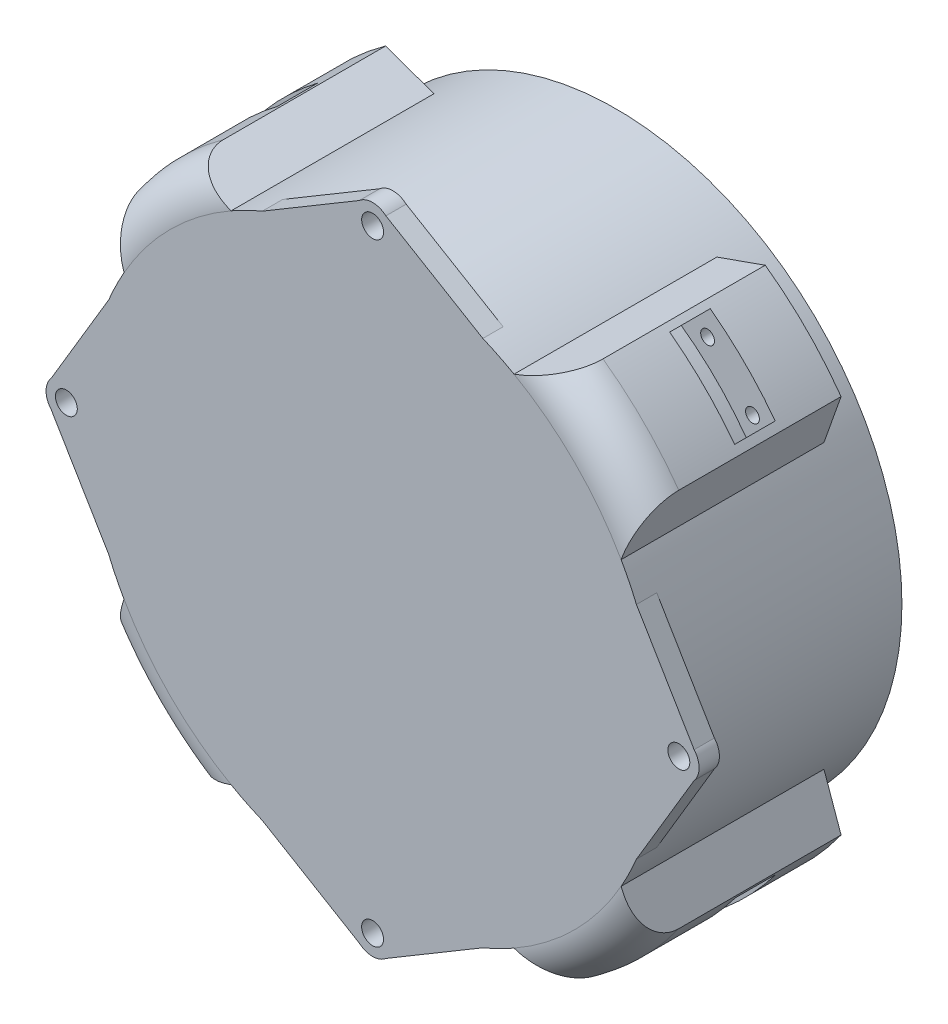
SolidWorks part; units mm, degrees
ref_plane "Front Plane" through (0, 0, 0) normal (0, 0, 1) x (1, 0, 0)
ref_plane "Top Plane" through (0, 0, 0) normal (0, 1, 0) x (1, 0, 0)
ref_plane "Right Plane" through (0, 0, 0) normal (1, 0, 0) x (0, 0, -1)
sketch "Sketch2" plane through (0, 0, 0) normal (0, 0, 1) x (1, 0, 0)
  line L1 (-38.5, -15.5) -> (-38.5, 15.5)
  line L2 (-33.5, 15.5) -> (33.5, 15.5)
  line L3 (-33.5, 15.5) -> (-33.5, -15.5)
  line L4 (-33.5, -15.5) -> (33.5, -15.5)
  line L5 (33.5, 15.5) -> (33.5, -15.5)
  line L6 (-33.5, 15.5) -> (33.5, -15.5) construction
  line L7 (-33.5, -15.5) -> (33.5, 15.5) construction
  line L8 (-38.5, 15.5) -> (-38.5, 20.5)
  line L9 (-38.5, 20.5) -> (33.5, 20.5)
  line L10 (0, -15.5) -> (0, -9.7241)
  line L11 (38.5, 20.5) -> (-33.5, 20.5)
  line L12 (38.5, 15.5) -> (38.5, 20.5)
  line L13 (38.5, -15.5) -> (38.5, 15.5)
  line L14 (38.5, -15.5) -> (38.5, -20.5)
  line L15 (38.5, -20.5) -> (-38.5, -20.5)
  line L16 (-38.5, -20.5) -> (-38.5, -15.5)
  line L17 (38.5, -20.5) -> (-38.5, -20.5)
  line L18 (38.5, -20.5) -> (38.5, 20.5)
  line L19 (38.5, 20.5) -> (-38.5, 20.5)
  line L20 (-38.5, -20.5) -> (-38.5, 20.5)
  point P2 (0, 0)
extrude "Boss-Extrude1" add sketch "Sketch2" against normal blind 30.4 contours L16 L15 L14 L13 L12 L11 L9 L8 L1 L2 L5 L4 L3 region at (-37.6276, 0, 0)
sketch "Sketch3" plane through (0, 0, 0) normal (0, 0, 1) x (1, 0, 0)
  line L1 (38.5, -20.5) -> (-38.5, -20.5)
  line L2 (38.5, -20.5) -> (38.5, 20.5)
  line L3 (38.5, 20.5) -> (-38.5, 20.5)
  line L4 (-38.5, -20.5) -> (-38.5, 20.5)
extrude "Boss-Extrude2" add sketch "Sketch3" along normal blind 5
sketch "Sketch4" plane through (-38.5, 0, 0) normal (-1, 0, 0) x (0, 0, 1)
  line L0 (5, 0) -> (0, 0)
  line L1 (5, 20.5) -> (5, -20.5) construction
  line L2 (0, 0) -> (-7, 0)
  line L4 (-10, -8) -> (-4, -8)
  line L5 (-10, -8) -> (-10, 8)
  line L6 (-10, 8) -> (-4, 8)
  line L7 (-4, -8) -> (-4, 8)
  line L8 (-10, -8) -> (-4, 8) construction
  line L9 (-10, 8) -> (-4, -8) construction
extrude "Cut-Extrude1" cut sketch "Sketch4" against normal blind 24 contours L4 L7 L6 L5 region at (-38.5, 0, -9.8291)
sketch "Sketch6" plane through (0, 0, 5) normal (0, 0, 1) x (1, 0, 0)
  circle A0 centre (-19.5, 0) radius 65.5
extrude "Boss-Extrude3" add sketch "Sketch6" against normal blind 5
sketch "Sketch7" plane through (0, 0, 5) normal (0, 0, 1) x (1, 0, 0)
  line L0 (-85, 0) -> (-90, 0)
  circle A1 centre (-19.5, 0) radius 65.5 construction
  circle A2 centre (-19.5, 0) radius 70.5
  circle A3 centre (-19.5, 0) radius 65.5
  circle M3 centre (-19.5, 0) radius 65.5
extrude "Boss-Extrude4" add sketch "Sketch7" against normal blind 60 contours A2 M3 region at (-19.5, 68.506, 5)
sketch "Sketch8" plane through (0, 0, 0) normal (0, 0, -1) x (-1, 0, 0)
  line L1 (19.5, -45.5) -> (29.5, -45.5)
  line L2 (29.5, -45.5) -> (29.5, -35.5)
  line L3 (29.5, -35.5) -> (9.5, -35.5)
  line L4 (9.5, -35.5) -> (9.5, -45.5)
  line L5 (9.5, -45.5) -> (19.9696, -45.5)
extrude "Boss-Extrude5" add sketch "Sketch8" along normal blind 56 contours L4 L5 L1 L2 L3 region at (-19.5, -40.5, 0)
ref_plane "Plane1" through (0, 0, 0) normal (0, -1, 0) x (-1, 0, 0)
sketch "Sketch17" plane through (-38.5, 0, 0) normal (-1, 0, 0) x (0, 0, 1)
  line L1 (-10, -8) -> (-4, -8)
  line L2 (-10, -8) -> (-10, 8)
  line L3 (-10, 8) -> (-4, 8)
  line L4 (-4, -8) -> (-4, 8)
extrude "Cut-Extrude7" cut sketch "Sketch17" along normal blind 64
sketch "Sketch19" plane through (0, -45.5, 0) normal (0, -1, 0) x (-1, 0, 0)
  line L0 (19.5, 56.8) -> (19.5, 52.8)
  line L1 (-51, 56.8) -> (90, 56.8) construction
  line L2 (9.5, 56) -> (17.1, 56)
  line L3 (9.5, 56) -> (29.5, 56) construction
  line L4 (21.9, 56) -> (29.5, 56)
  line L5 (13.3, 56) -> (9.5, 0)
  line L6 (25.7, 56) -> (29.5, 0)
  line L7 (29.5, 0) -> (29.5, 54.5391)
  line L8 (29.5, 56) -> (29.5, 0) construction
  line L9 (9.5, 0) -> (9.5, 55.2956)
  line L10 (9.5, 56) -> (9.5, 0) construction
  circle A0 centre (19.5, 52.8) radius 1.7
  circle A1 centre (19.5, 52.8) radius 4
  line M5 (29.5, 0) -> (29.5, 56)
  line M6 (29.5, 56) -> (9.5, 56)
  line M7 (9.5, 56) -> (9.5, 0)
extrude "Cut-Extrude8" cut sketch "Sketch19" against normal blind 11 contours L5 L2 M7 | L6 M6 M5 | A0 region at (-28.2333, -45.5, -37.3333) region at (-10.7667, -45.5, -37.3333) region at (-20.6681, -45.5, -53.9681)
fillet "Fillet1" radius 2 2 edges at (-13.3, -40.5, -56) (-25.7, -40.5, -56)
sketch "Sketch20" plane through (0, 0, -56) normal (0, 0, -1) x (-1, 0, 0)
  line L0 (13.1735, -40.5) -> (13.1735, -38.3)
  line L1 (13.1735, -45.5) -> (13.1735, -35.5) construction
  line L2 (13.1735, -40.5) -> (13.1735, -42.7)
  line L3 (13.1735, -42.7) -> (44.2341, -42.7)
  line L4 (44.2341, -42.7) -> (44.2341, -38.3)
  line L5 (44.2341, -38.3) -> (3.3181, -38.3)
  line L6 (3.3181, -38.3) -> (3.3181, -42.7)
  line L7 (3.3181, -42.7) -> (13.1735, -42.7)
  line M8 (15.1689, -35.5) -> (15.1689, -45.5)
  line M10 (23.8311, -45.5) -> (23.8311, -35.5)
extrude "Cut-Extrude9" cut sketch "Sketch20" against normal blind 10 contours L4 L5 L3 M10 | L6 L7 L2 L0 L5 | L5 L3 M10 M8 | L5 L0 L2 L3 M8 region at (-8.2458, -40.5, -56) region at (-14.1712, -40.5, -56) region at (-19.5, -40.5, -56) region at (-34.0326, -40.5, -56)
ref_plane "Plane2" through (0, 0, 0) normal (0, -1, 0) x (-1, 0, 0)
mirror "Mirror1" about plane through (0, 0, 0) normal (0, -1, 0) of "Boss-Extrude5", "Cut-Extrude8", "Cut-Extrude9"
fillet "Fillet2" radius 2 4 edges at (-13.3, 44.1, -56) (-13.3, 36.9, -56) (-25.7, 44.1, -56) (-25.7, 36.9, -56)
sketch "Sketch22" plane through (0, 0, 0) normal (0, 0, -1) x (-1, 0, 0)
  line L0 (85, 0) -> (65, 0)
  line L1 (65, 0) -> (65, -10)
  line L2 (65, -10) -> (55, -10)
  line L3 (55, -10) -> (55, 11.1249)
  line L4 (55, 11.1249) -> (65, 11.1249)
  line L5 (65, 11.1249) -> (65, 0)
  circle A0 centre (19.5, 0) radius 65.5 construction
extrude "Boss-Extrude6" add sketch "Sketch22" along normal up to surface (56 mm away) contours L5 L4 L3 L2 L1 region at (-60, 0.5625, 0) up to face at (-19.5, -36.9, -56)
sketch "Sketch23" plane through (-65, 0, 0) normal (-1, 0, 0) x (0, 0, 1)
  line L1 (-56, -10) -> (-56, -6.2)
  line L3 (-56, 11.1249) -> (-56, 6.7625)
  line L4 (-56, -6.2) -> (0, -10)
  line L5 (0, -10) -> (-55.4574, -10)
  line L6 (-56, -10) -> (0, -10) construction
  line L7 (-56, 11.1249) -> (0.5239, 11.1249)
  line L8 (0.5239, 11.1249) -> (-56, 6.7625)
  line L9 (-56, -10) -> (-55.4574, -10)
  circle A0 centre (-52.8, 0) radius 1.7
sketch "Sketch24" plane through (-65, 0, 0) normal (-1, 0, 0) x (0, 0, 1)
extrude "Cut-Extrude10" cut sketch "Sketch23" against normal up to surface (10 mm away) contours L3 L8 L7 | L1 L4 L5 L9 | A0 up to face at (-55, 0.5625, -28)
fillet "Fillet3" radius 2 2 edges at (-60, -6.2, -56) (-60, 6.7625, -56)
sketch "Sketch25" plane through (0, 0, -56) normal (0, 0, -1) x (-1, 0, 0)
  line L0 (60, -4.3311) -> (60, -11.7911)
  line L1 (55, -4.3311) -> (65, -4.3311) construction
  line L2 (60, -11.7911) -> (57.8, -11.7911)
  line L3 (60, -11.7911) -> (62.2, -11.7911)
  line L4 (62.2, -11.7911) -> (62.2, 15.1058)
  line L5 (62.2, 15.1058) -> (57.8, 15.1058)
  line L6 (57.8, 15.1058) -> (57.8, -11.7911)
  line M3 (55, -4.3311) -> (65, -4.3311)
  line M5 (65, 4.9109) -> (55, 4.9109)
extrude "Cut-Extrude11" cut sketch "Sketch25" against normal blind 10 contours L5 L6 L4 M5 | L6 L4 M5 M3 | L3 L4 L0 M3 | L6 L2 L0 M3 region at (-61.1, -8.0611, -56) region at (-58.9, -8.0611, -56) region at (-60, 0.2899, -56) region at (-60, 10.0083, -56)
sketch "Sketch28" plane through (0, 0, -30.4) normal (0, 0, -1) x (-1, 0, 0)
  line L0 (3.6887, -26.8754) -> (9.5226, -20.5)
  line L1 (-38.5, -20.5) -> (38.5, -20.5) construction
  line L2 (3.6887, -26.8754) -> (9.5226, -20.5) construction
  line L3 (9.5226, -20.5) -> (-9.2108, -20.5)
  line L4 (-9.2108, -20.5) -> (-9.5226, -20.5)
  line L5 (-3.6887, -26.8754) -> (-9.5226, -20.5) construction
  line L6 (-9.5226, -20.5) -> (-3.6887, -26.8754)
  line L7 (-24.7605, 0) -> (-19.403, 0)
  line L8 (-24.7605, 12) -> (-24.7605, -12) construction
  line L9 (-9.5226, 20.5) -> (-3.6887, 26.8754)
  line L10 (-9.2108, 20.5) -> (-9.5226, 20.5)
  line L11 (9.5226, 20.5) -> (-9.2108, 20.5)
  line L12 (3.6887, 26.8754) -> (9.5226, 20.5)
  circle A0 centre (0, -23.5) radius 1.7
  arc A1 (-3.6887, -26.8754) -> (3.6887, -26.8754) centre (0, -23.5) ccw
  arc A2 (-3.6887, 26.8754) -> (3.6887, 26.8754) centre (0, 23.5) cw
  circle A3 centre (0, 23.5) radius 1.7
  line M9 (38.5, 20.5) -> (-38.5, 20.5)
  line M11 (-38.5, -20.5) -> (38.5, -20.5)
extrude "Boss-Extrude7" add sketch "Sketch28" against normal blind 5 contours L6 A1 L0 A0 M11 | A2 L9 L12 A3 M9 region at (0, -28.2934, -30.4) region at (6.4533, 23.5483, -30.4)
sketch "Sketch30" plane through (0, 0, 5) normal (0, 0, 1) x (1, 0, 0)
  line L0 (-46.6821, 65.0491) -> (-22.7837, 79.2706)
  line L1 (7.6821, 65.0491) -> (-16.2163, 79.2706)
  line L2 (45.5491, 27.1821) -> (59.7706, 3.2837)
  line L3 (45.5491, -27.1821) -> (59.7706, -3.2837)
  line L4 (7.6821, -65.0491) -> (-16.2163, -79.2706)
  line L5 (-46.6821, -65.0491) -> (-22.7837, -79.2706)
  line L6 (-84.5491, -27.1821) -> (-98.7706, -3.2837)
  line L7 (-84.5491, 27.1821) -> (-98.7706, 3.2837)
  circle A0 centre (-19.5, 0) radius 70.5 construction
  circle A1 centre (-19.5, 75.5) radius 2.7
  arc A2 (-16.2163, 79.2706) -> (-22.7837, 79.2706) centre (-19.5, 75.5) ccw
  arc A3 (7.6821, 65.0491) -> (-46.6821, 65.0491) centre (-19.5, 0) ccw
  circle A4 centre (56, 0) radius 2.7
  arc A5 (59.7706, -3.2837) -> (59.7706, 3.2837) centre (56, 0) ccw
  arc A6 (45.5491, -27.1821) -> (45.5491, 27.1821) centre (-19.5, 0) ccw
  circle A7 centre (-19.5, -75.5) radius 2.7
  arc A8 (-22.7837, -79.2706) -> (-16.2163, -79.2706) centre (-19.5, -75.5) ccw
  arc A9 (-46.6821, -65.0491) -> (7.6821, -65.0491) centre (-19.5, 0) ccw
  circle A10 centre (-95, 0) radius 2.7
  arc A11 (-98.7706, 3.2837) -> (-98.7706, -3.2837) centre (-95, 0) ccw
  arc A12 (-84.5491, 27.1821) -> (-84.5491, -27.1821) centre (-19.5, 0) ccw
  point P31 (-19.5, 0)
  dimension "D1" = 4
extrude "Boss-Extrude8" add sketch "Sketch30" against normal blind 5
sketch "Sketch31" plane through (0, 0, 0) normal (0, 0, -1) x (-1, 0, 0)
  line L0 (-30.351, -49.851) -> (-37.4221, -56.9221)
  line L1 (-27.3029, -65.4961) -> (-15.3724, -61.2712)
  line L2 (-45.9961, -46.8029) -> (-41.7713, -34.8724)
  line L3 (-30.351, 49.851) -> (-37.4221, 56.9221)
  line L4 (-45.9961, 46.8029) -> (-41.7712, 34.8724)
  line L5 (-27.3029, 65.4961) -> (-15.3724, 61.2713)
  line L6 (69.351, 49.851) -> (76.4221, 56.9221)
  line L7 (66.3029, 65.4961) -> (54.3724, 61.2712)
  line L8 (84.9961, 46.8029) -> (80.7713, 34.8724)
  line L9 (69.351, -49.851) -> (76.4221, -56.9221)
  line L10 (84.9961, -46.8029) -> (80.7712, -34.8724)
  line L11 (66.3029, -65.4961) -> (54.3724, -61.2713)
  arc A0 (-45.9961, -46.8029) -> (-27.3029, -65.4961) centre (19.5, 0) ccw
  arc A1 (-41.7713, -34.8724) -> (-15.3724, -61.2712) centre (19.5, 0) ccw
  arc A2 (-27.3029, 65.4961) -> (-45.9961, 46.8029) centre (19.5, 0) ccw
  arc A3 (-15.3724, 61.2713) -> (-41.7712, 34.8724) centre (19.5, 0) ccw
  arc A4 (84.9961, 46.8029) -> (66.3029, 65.4961) centre (19.5, 0) ccw
  arc A5 (80.7713, 34.8724) -> (54.3724, 61.2712) centre (19.5, 0) ccw
  arc A6 (66.3029, -65.4961) -> (84.9961, -46.8029) centre (19.5, 0) ccw
  arc A7 (54.3724, -61.2713) -> (80.7712, -34.8724) centre (19.5, 0) ccw
  point P29 (19.5, 0)
  dimension "D1" = 4
extrude "Boss-Extrude9" add sketch "Sketch31" along normal up to surface (55 mm away) and the other way blind 5 contours A1 L0 A0 L1 | A1 L2 A0 L0 | A3 L3 A2 L4 | A3 L5 A2 L3 | A5 L8 A4 L6 | A5 L6 A4 L7 | A7 L9 A6 L10 | A7 L11 A6 L9 region at (27.5596, -58.4658, 0) region at (38.9658, -47.0596, 0) region at (38.9658, 47.0596, 0) region at (27.5596, 58.4658, 0) region at (-66.5596, 58.4658, 0) region at (-77.9658, 47.0596, 0) region at (-77.9658, -47.0596, 0) region at (-66.5596, -58.4658, 0) up to face at (51, 0, -55)
fillet "Fillet4" radius 10 8 edges at (37.4221, 56.9221, 5) (37.4221, 56.9221, -55) (-76.4221, 56.9221, 5) (-76.4221, 56.9221, -55) (-76.4221, -56.9221, -55) (-76.4221, -56.9221, 5) (37.4221, -56.9221, 5) (37.4221, -56.9221, -55)
sketch "Sketch32" plane through (0, 0, -55) normal (0, 0, -1) x (-1, 0, 0)
  circle A0 centre (19.5, 0) radius 70.5
  circle A1 centre (19.5, 0) radius 80.5
extrude "Cut-Extrude12" cut sketch "Sketch32" against normal up to vertex (10 mm away) up to point (27.3029, -65.4961, -45)
sketch "Sketch33" plane through (0, 0, -45) normal (0, 0, -1) x (-1, 0, 0)
  circle A3 centre (-39.1586, 46.9103) radius 1.7
  circle A4 centre (-28.0836, 58.0553) radius 1.7
  circle A5 centre (66.4103, 58.6586) radius 1.7
  circle A6 centre (77.5553, 47.5836) radius 1.7
  circle A7 centre (78.1586, -46.9103) radius 1.7
  circle A8 centre (67.0836, -58.0553) radius 1.7
  circle A9 centre (-27.4103, -58.6586) radius 1.7
  circle A10 centre (-38.5553, -47.5836) radius 1.7
  point P19 (19.5, 0)
  dimension "D1" = 4
extrude "Cut-Extrude13" cut sketch "Sketch33" against normal blind 20
ref_plane "Plane3" through (0, 0, -25) normal (0, 0, -1) x (-1, 0, 0)
sketch "Sketch35" plane through (0, 0, -25) normal (0, 0, -1) x (-1, 0, 0)
  line L0 (-44.9435, -48.2419) -> (-40.4766, -37.0549)
  line L1 (-28.9778, -64.2662) -> (-17.8459, -59.7957)
  line L2 (-28.7419, 64.4435) -> (-17.5549, 59.9766)
  line L3 (-44.7662, 48.4778) -> (-40.2957, 37.3459)
  line L4 (83.9435, 48.2419) -> (79.4766, 37.0549)
  line L5 (67.9778, 64.2662) -> (56.8459, 59.7957)
  line L6 (67.7419, -64.4435) -> (56.5549, -59.9766)
  line L7 (83.7662, -48.4778) -> (79.2957, -37.3459)
  arc A0 (-44.9435, -48.2419) -> (-28.9778, -64.2662) centre (19.5, 0) ccw
  arc A1 (-40.4766, -37.0549) -> (-17.8459, -59.7957) centre (19.5, 0) ccw
  arc A2 (-28.7419, 64.4435) -> (-44.7662, 48.4778) centre (19.5, 0) ccw
  arc A3 (-17.5549, 59.9766) -> (-40.2957, 37.3459) centre (19.5, 0) ccw
  arc A4 (83.9435, 48.2419) -> (67.9778, 64.2662) centre (19.5, 0) ccw
  arc A5 (79.4766, 37.0549) -> (56.8459, 59.7957) centre (19.5, 0) ccw
  arc A6 (67.7419, -64.4435) -> (83.7662, -48.4778) centre (19.5, 0) ccw
  arc A7 (56.5549, -59.9766) -> (79.2957, -37.3459) centre (19.5, 0) ccw
  point P22 (19.5, 0)
  dimension "D1" = 4
extrude "Cut-Extrude14" cut sketch "Sketch35" along normal blind 5 and the other way blind 5
